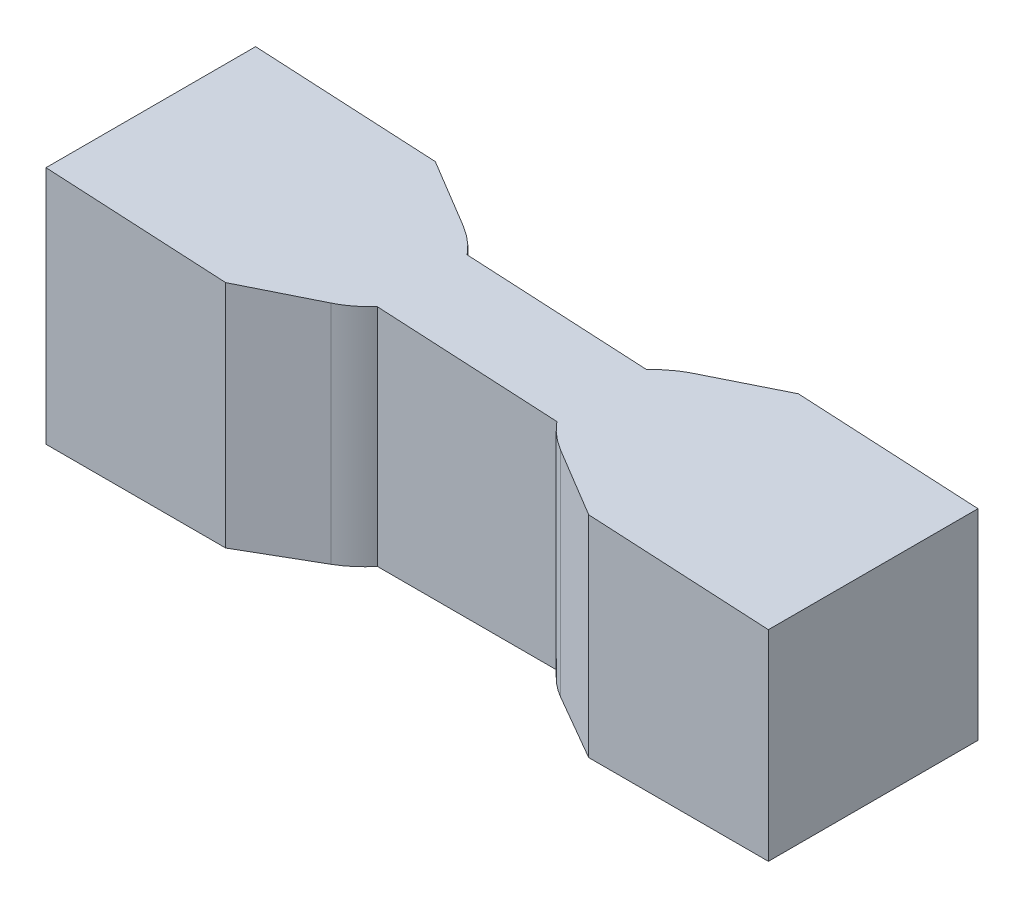
SolidWorks part; units mm, degrees
ref_plane "Front Plane" through (0, 0, 0) normal (0, 0, 1) x (1, 0, 0)
ref_plane "Top Plane" through (0, 0, 0) normal (0, 1, 0) x (1, 0, 0)
ref_plane "Right Plane" through (0, 0, 0) normal (1, 0, 0) x (0, 0, -1)
sketch "Sketch1" plane through (0, 0, 0) normal (0, 1, 0) x (1, 0, 0)
  line L0 (-5.0161, 2.5988) -> (-5.3344, -0.3843) construction
  line L1 (3, -1.5) -> (-3, -1.5)
  line L2 (3, -1.5) -> (3, 1.5) construction
  line L3 (3, 1.5) -> (-3, 1.5)
  line L4 (-3, -1.5) -> (-3, 1.5) construction
  line L5 (3, -1.5) -> (-3, 1.5) construction
  line L6 (3, 1.5) -> (-3, -1.5) construction
  line L7 (-5.3344, -0.3843) -> (-3, 1.5) construction
  line L8 (-5.3344, 0.3843) -> (-5.0161, -2.5988) construction
  line L9 (-5.3344, 0.3843) -> (-3, -1.5) construction
  line L10 (0, 0) -> (-3.8344, -2.2138) construction
  line L11 (0, 0) -> (3.8344, -2.2138) construction
  line L12 (0, 1.5) -> (0, -1.5) construction
  line L13 (0, 0) -> (-3.8344, 2.2138) construction
  line L14 (0, 0) -> (3.8344, 2.2138) construction
  line L15 (3, 1.5) -> (5.3344, -0.3843) construction
  line L16 (5.3344, -0.3843) -> (5.0161, 2.5988) construction
  line L17 (5.0161, -2.5988) -> (5.3344, 0.3843) construction
  line L18 (5.3344, 0.3843) -> (3, -1.5) construction
  line L19 (-5.8941, 1.8095) -> (-5.8941, -1.8095)
  line L20 (5.8941, 1.8095) -> (5.8941, -1.8095)
  arc A0 (-3, -1.5) -> (-5.0161, -2.5988) centre (-5.3344, 0.3843) cw
  arc A1 (-3, 1.5) -> (-5.0161, 2.5988) centre (-5.3344, -0.3843) ccw
  arc A2 (3, 1.5) -> (5.0161, 2.5988) centre (5.3344, -0.3843) cw
  arc A3 (3, -1.5) -> (5.0161, -2.5988) centre (5.3344, 0.3843) ccw
  arc A4 (-5.0161, 2.5988) -> (-5.8941, 1.8095) centre (-5.1003, 1.8095) ccw
  arc A5 (-5.0161, -2.5988) -> (-5.8941, -1.8095) centre (-5.1003, -1.8095) cw
  arc A6 (5.0161, -2.5988) -> (5.8941, -1.8095) centre (5.1003, -1.8095) ccw
  arc A7 (5.0161, 2.5988) -> (5.8941, 1.8095) centre (5.1003, 1.8095) cw
  point P0 (0, 0)
  dimension "D5" = 45
  dimension "D8" = 45
  dimension "D11" = 3
  dimension "D10" = 0.7937
  dimension "D2" = 3
  dimension "D3" = 120
  dimension "D4" = 60
  dimension "D6" = 45
  dimension "D7" = 120
  dimension "D9" = 45
  dimension "D12" = 6
sketch "Sketch2" plane through (0, 0, 0) normal (0, 1, 0) x (1, 0, 0)
  line L1 (-6.0622, 3.5) -> (-12.0622, 3.5)
  line L2 (-6.0622, 3.5) -> (-6.0622, -3.5) construction
  line L3 (-6.0622, -3.5) -> (-12.0622, -3.5)
  line L4 (-12.0622, 3.5) -> (-12.0622, -3.5)
  line L5 (3.8344, 2.2138) -> (6.0622, 3.5)
  line L6 (6.0622, 3.5) -> (12.0622, 3.5)
  line L7 (6.0622, 3.5) -> (6.0622, -3.5) construction
  line L9 (-3, 1.5) -> (-3, -1.5)
  line L10 (6.0622, -3.5) -> (12.0622, -3.5)
  line L11 (-3.8344, -2.2138) -> (-6.0622, -3.5)
  line L12 (-3.8344, 2.2138) -> (-6.0622, 3.5)
  line L13 (12.0622, 3.5) -> (12.0622, -3.5)
  line L15 (3.8344, -2.2138) -> (6.0622, -3.5)
  line L16 (3, 1.5) -> (3, -1.5)
  arc A0 (3.8344, 2.2138) -> (3, 1.5) centre (5.3344, -0.3843) ccw
  arc A1 (-3, 1.5) -> (-5.0161, 2.5988) centre (-5.3344, -0.3843) ccw construction
  arc A2 (3.8344, -2.2138) -> (3, -1.5) centre (5.3344, 0.3843) cw
  arc A4 (5.0161, 2.5988) -> (3, 1.5) centre (5.3344, -0.3843) ccw construction
  arc A6 (3, -1.5) -> (5.0161, -2.5988) centre (5.3344, 0.3843) ccw construction
  arc A7 (-5.0161, -2.5988) -> (-3, -1.5) centre (-5.3344, 0.3843) ccw construction
  arc A10 (-3.8344, 2.2138) -> (-3, 1.5) centre (-5.3344, -0.3843) cw
  arc A11 (-3.8344, -2.2138) -> (-3, -1.5) centre (-5.3344, 0.3843) ccw
  dimension "D1" = 7
  dimension "D2" = 6
sketch "Sketch3" plane through (0, 0, 0) normal (0, 1, 0) x (1, 0, 0)
  line L0 (-12.0622, 3.5) -> (-12.0622, -3.5) construction
  line L2 (12.0622, 3.5) -> (12.0622, -3.5) construction
  circle A0 centre (-9.0622, 0) radius 1.55
  circle A1 centre (9.0622, 0) radius 1.55
  dimension "D1" = 3.1
  dimension "D2" = 3
  dimension "D3" = 3
extrude "Boss-Extrude1" add sketch "Sketch2" along normal blind 8
extrude "Boss-Extrude2" add sketch "Sketch1" along normal up to surface (8 mm away) up to face at (-6.2315, 8, 0)
extrude "Cut-Extrude1" [suppressed] cut sketch "Sketch3" along normal through all
sketch "Sketch4" plane through (0, 0, 0) normal (0, 0, 1) x (1, 0, 0)
  line L0 (12.0622, 8) -> (12.0622, 6.7)
  line L1 (12.0622, 8) -> (12.0622, 0) construction
  line L2 (12.0622, 6.7) -> (-12.0622, 8)
  line L3 (-12.0622, 8) -> (12.0622, 8)
  dimension "D1" = 1.3
extrude "Cut-Extrude2" cut sketch "Sketch4" against normal through all both and the other way through all
ref_axis "Axis1" through (3, 7.1883, 1.5) along (0, 0, -1)
ref_plane "Plane1" through (0, 7.1883, 0) normal (0, 1, 0) x (1, 0, 0)
sketch "Sketch5" plane through (0, 7.1883, 0) normal (0, 1, 0) x (1, 0, 0)
  line L1 (-3.8344, 2.2138) -> (3.8344, 2.2138)
  line L2 (-3.8344, 2.2138) -> (-3.8344, -2.2138)
  line L3 (-3.8344, -2.2138) -> (3.8344, -2.2138)
  line L4 (3.8344, 2.2138) -> (3.8344, -2.2138)
sketch "Sketch6" plane through (0, 0, 0) normal (0, -1, 0) x (1, 0, 0)
  line L12 (-3.8344, 2.2138) -> (-6.0622, 3.5)
  line L13 (-6.0622, 3.5) -> (-12.0622, 3.5)
  line L14 (-12.0622, 3.5) -> (-12.0622, -3.5)
  line L15 (-12.0622, -3.5) -> (-6.0622, -3.5)
  line L16 (-6.0622, -3.5) -> (-3.8344, -2.2138)
  line L17 (-3, -1.5) -> (3, -1.5)
  line L18 (3.8344, -2.2138) -> (6.0622, -3.5)
  line L19 (6.0622, -3.5) -> (12.0622, -3.5)
  line L20 (12.0622, -3.5) -> (12.0622, 3.5)
  line L21 (12.0622, 3.5) -> (6.0622, 3.5)
  line L22 (6.0622, 3.5) -> (3.8344, 2.2138)
  line L23 (3, 1.5) -> (-3, 1.5)
  line L24 (-3.8344, 2.2138) -> (-6.0622, 3.5)
  line L25 (-6.0622, 3.5) -> (-12.0622, 3.5)
  line L26 (-12.0622, 3.5) -> (-12.0622, -3.5)
  line L27 (-12.0622, -3.5) -> (-6.0622, -3.5)
  line L28 (-6.0622, -3.5) -> (-3.8344, -2.2138)
  line L29 (-3, -1.5) -> (3, -1.5)
  line L30 (3.8344, -2.2138) -> (6.0622, -3.5)
  line L31 (6.0622, -3.5) -> (12.0622, -3.5)
  line L32 (12.0622, -3.5) -> (12.0622, 3.5)
  line L33 (12.0622, 3.5) -> (6.0622, 3.5)
  line L34 (6.0622, 3.5) -> (3.8344, 2.2138)
  line L35 (3, 1.5) -> (-3, 1.5)
  arc A4 (-3, 1.5) -> (-3.8344, 2.2138) centre (-5.3344, -0.3843) ccw
  arc A5 (-3.8344, -2.2138) -> (-3, -1.5) centre (-5.3344, 0.3843) ccw
  arc A6 (3, -1.5) -> (3.8344, -2.2138) centre (5.3344, 0.3843) ccw
  arc A7 (3.8344, 2.2138) -> (3, 1.5) centre (5.3344, -0.3843) ccw
  arc A8 (-3, 1.5) -> (-3.8344, 2.2138) centre (-5.3344, -0.3843) ccw
  arc A9 (-3.8344, -2.2138) -> (-3, -1.5) centre (-5.3344, 0.3843) ccw
  arc A10 (3, -1.5) -> (3.8344, -2.2138) centre (5.3344, 0.3843) ccw
  arc A11 (3.8344, 2.2138) -> (3, 1.5) centre (5.3344, -0.3843) ccw
  dimension "D1" = 0
